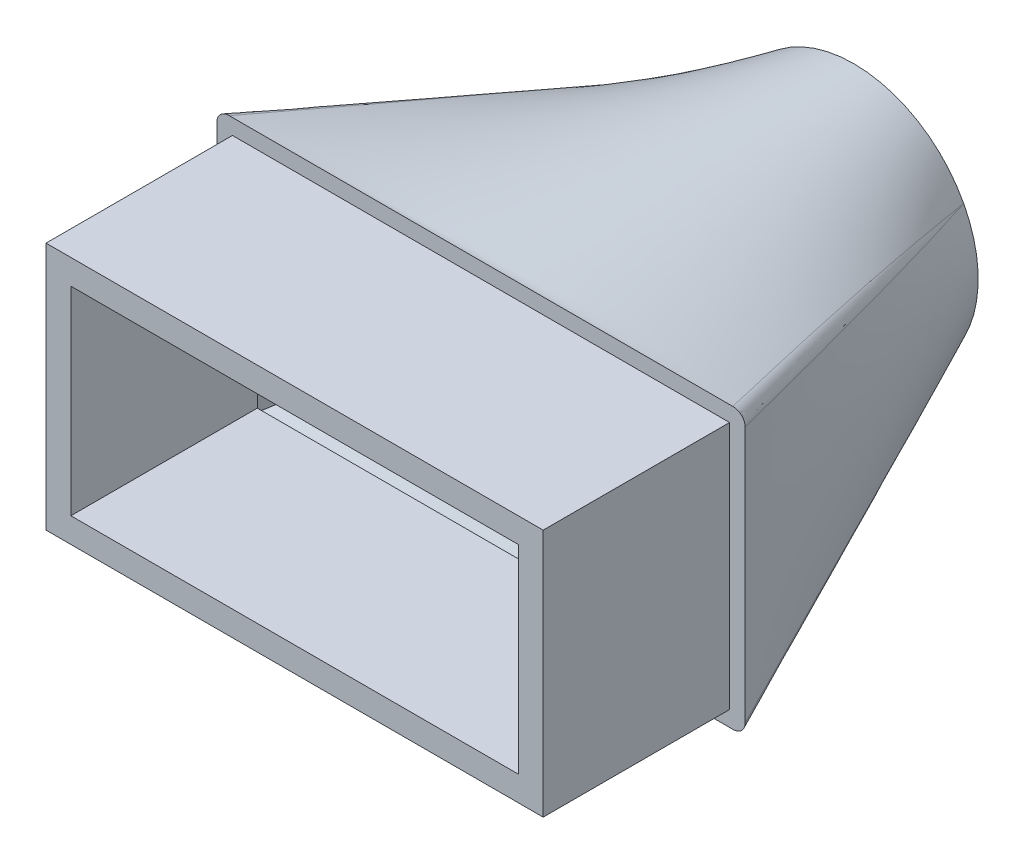
SolidWorks part; units mm, degrees
ref_plane "Front Plane" through (0, 0, 0) normal (0, 0, 1) x (1, 0, 0)
ref_plane "Top Plane" through (0, 0, 0) normal (0, 1, 0) x (1, 0, 0)
ref_plane "Right Plane" through (0, 0, 0) normal (1, 0, 0) x (0, 0, -1)
sketch "Sketch2" plane through (0, 0, 0) normal (0, 0, 1) x (1, 0, 0)
  circle A0 centre (0, 0) radius 25.4
  dimension "D1" = 50.8
ref_plane "Plane1" through (0, 0, 76.2) normal (0, 0, 1) x (1, 0, 0)
sketch "Sketch3" plane through (0, 0, 76.2) normal (0, 0, 1) x (1, 0, 0)
  line L1 (53.975, -28.575) -> (-53.975, -28.575)
  line L2 (53.975, -28.575) -> (53.975, 28.575)
  line L3 (53.975, 28.575) -> (-53.975, 28.575)
  line L4 (-53.975, -28.575) -> (-53.975, 28.575)
  line L5 (53.975, -28.575) -> (-53.975, 28.575) construction
  line L6 (53.975, 28.575) -> (-53.975, -28.575) construction
  point P0 (0, 0)
  dimension "D1" = 107.95
  dimension "D2" = 57.15
loft "Loft1" add profiles "Sketch2", "Sketch3" connector at (10.0289, 23.3362, 0) connector at (53.975, 28.575, 76.2)
shell "Shell1" thickness 5.08 removed face at (0, 0, 76.2)
sketch "Sketch5" plane through (0, 0, 76.2) normal (0, 0, 1) x (1, 0, 0)
  line L1 (50.8, -25.4) -> (-50.8, -25.4)
  line L2 (50.8, -25.4) -> (50.8, 25.4)
  line L3 (50.8, 25.4) -> (-50.8, 25.4)
  line L4 (-50.8, -25.4) -> (-50.8, 25.4)
  line L5 (50.8, -25.4) -> (-50.8, 25.4) construction
  line L6 (50.8, 25.4) -> (-50.8, -25.4) construction
  line L7 (45.72, -20.32) -> (-45.72, -20.32)
  line L8 (45.72, -20.32) -> (45.72, 20.32)
  line L9 (45.72, 20.32) -> (-45.72, 20.32)
  line L10 (-45.72, -20.32) -> (-45.72, 20.32)
  line L11 (45.72, -20.32) -> (-45.72, 20.32) construction
  line L12 (45.72, 20.32) -> (-45.72, -20.32) construction
  point P0 (0, 0)
  point P6 (0, 0)
  dimension "D1" = 50.8
  dimension "D2" = 101.6
  dimension "D3" = 5.08
  dimension "D4" = 5.08
extrude "Boss-Extrude2" add sketch "Sketch5" along normal blind 38.1 contours L3 L4 L1 L2 | L9 L10 L7 L8
fillet "Fillet2" radius 2.54 4 edges
sketch "Sketch7" plane through (0, 0, 0) normal (0, 0, -1) x (-1, 0, 0)
  circle A0 centre (0, 0) radius 5
  circle A1 centre (0, 8) radius 2
  circle A2 centre (9.65, 0) radius 2
  circle A3 centre (-9.65, 0) radius 2
  circle A4 centre (0, -8) radius 2
  circle A5 centre (11.6539, -9.65) radius 5
  dimension "D1" = 4
  dimension "D2" = 4
  dimension "D3" = 4
  dimension "D4" = 4
  dimension "D5" = 10
  dimension "D6" = 9.65
  dimension "D8" = 8
  dimension "D9" = 8
  dimension "D10" = 10
  dimension "9.65" = 9.65
extrude "Cut-Extrude2" cut sketch "Sketch7" against normal through all
